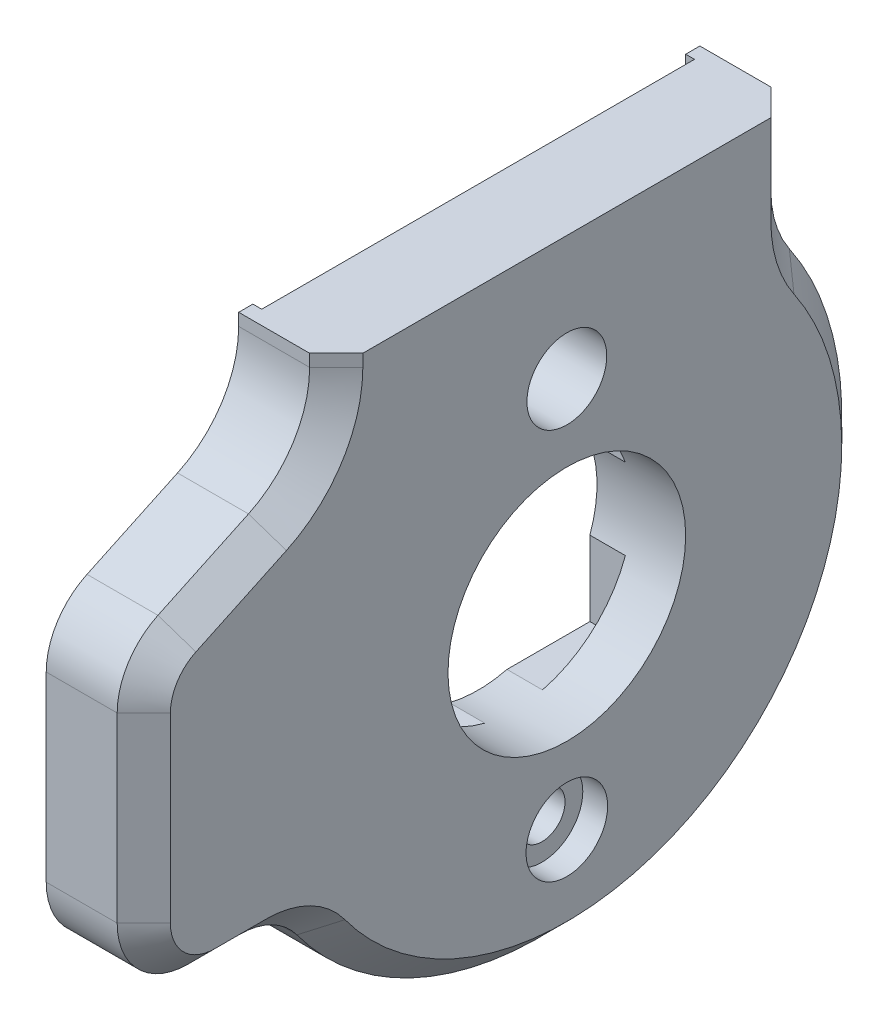
SolidWorks part; units mm, degrees
ref_plane "Front Plane" through (0, 0, 0) normal (0, 0, 1) x (1, 0, 0)
ref_plane "Top Plane" through (0, 0, 0) normal (0, 1, 0) x (1, 0, 0)
ref_plane "Right Plane" through (0, 0, 0) normal (1, 0, 0) x (0, 0, -1)
sketch "Sketch1" plane through (0, 0, 0) normal (1, 0, 0) x (0, 0, -1)
  line L0 (-53, 3.3371) -> (-53, -7.0385)
  line L1 (-82.9482, -28.4) -> (-85.85, -28.4)
  line L2 (-89.85, -24.4) -> (-89.85, -14.1397)
  line L3 (-87.5516, -10.5196) -> (-82.4476, -8.1205)
  line L4 (-79, -2.6905) -> (-79, 3.3371)
  arc A0 (-80.25, 7.0028) -> (-51.75, 7.0028) centre (-66, 18) cw
  arc A1 (-51.75, 7.0028) -> (-53, 3.3371) centre (-47, 3.3371) ccw
  arc A2 (-53, -7.0385) -> (-51.9565, -10.4198) centre (-47, -7.0385) ccw
  arc A3 (-51.9565, -10.4198) -> (-79.7199, -30.0381) centre (-66, -20) cw
  arc A4 (-79.7199, -30.0381) -> (-82.9482, -28.4) centre (-82.9482, -32.4) ccw
  arc A5 (-85.85, -28.4) -> (-89.85, -24.4) centre (-85.85, -24.4) cw
  arc A6 (-89.85, -14.1397) -> (-87.5516, -10.5196) centre (-85.85, -14.1397) cw
  arc A7 (-82.4476, -8.1205) -> (-79, -2.6905) centre (-85, -2.6905) ccw
  arc A8 (-79, 3.3371) -> (-80.25, 7.0028) centre (-85, 3.3371) ccw
extrude "Boss-Extrude1" add sketch "Sketch1" along normal blind 5.5 from offset 55.1
sketch "Sketch2" plane through (0, 0, 0) normal (1, 0, 0) x (0, 0, -1)
  line L0 (-53.8, 3.3371) -> (-53.8, -7.0385)
  line L1 (-82.9482, -27.6) -> (-85.85, -27.6)
  line L2 (-89.05, -24.4) -> (-89.05, -14.1397)
  line L3 (-87.2113, -11.2436) -> (-82.1073, -8.8446)
  line L4 (-78.2, -2.6905) -> (-78.2, 3.3371)
  arc A0 (-79.6167, 7.4916) -> (-52.3833, 7.4916) centre (-66, 18) cw
  arc A1 (-52.3833, 7.4916) -> (-53.8, 3.3371) centre (-47, 3.3371) ccw
  arc A2 (-53.8, -7.0385) -> (-52.6174, -10.8706) centre (-47, -7.0385) ccw
  arc A3 (-52.6174, -10.8706) -> (-79.0743, -29.5657) centre (-66, -20) cw
  arc A4 (-79.0743, -29.5657) -> (-82.9482, -27.6) centre (-82.9482, -32.4) ccw
  arc A5 (-85.85, -27.6) -> (-89.05, -24.4) centre (-85.85, -24.4) cw
  arc A6 (-89.05, -14.1397) -> (-87.2113, -11.2436) centre (-85.85, -14.1397) cw
  arc A7 (-82.1073, -8.8446) -> (-78.2, -2.6905) centre (-85, -2.6905) ccw
  arc A8 (-78.2, 3.3371) -> (-79.6167, 7.4916) centre (-85, 3.3371) ccw
extrude "Boss-Extrude2" add sketch "Sketch2" along normal blind 0.6 from offset 55 separate body
combine bodies "Combine1" operation type subtract main body 101 bodies to subtract 102
chamfer "Chamfer1" distance 1.5 angle 45 14 edges at (60.6, -5.9065, 79.9347) (60.6, -9.3201, 84.9996) (60.6, 0.3233, 79) (60.6, -11.9956, 89.2269) (60.6, 5.2736, 79.3211) (60.6, -19.2698, 89.85) (60.6, 36, 66) (60.6, -27.2284, 88.6784) (60.6, 5.2736, 52.6789) (60.6, -28.4, 84.3991) (60.6, -1.8507, 53) (60.6, -28.833, 81.1381) (60.6, -8.8078, 52.7332) (60.6, -33.8836, 56.1895)
sketch "Sketch3" plane through (0, 0, 0) normal (0, 0, 1) x (1, 0, 0)
  line L1 (55.5, -21) -> (59.6, -21)
  line L2 (55.5, -21) -> (55.5, -19)
  line L3 (55.5, -19) -> (59.6, -19)
  line L4 (59.6, -21) -> (59.6, -19)
extrude "Boss-Extrude3" add sketch "Sketch3" along normal blind 2.9 from offset 55.875 separate body
combine bodies "Combine2" operation type subtract main body 103 bodies to subtract 104
sketch "Sketch4" plane through (0, 0, 0) normal (0, 0, 1) x (1, 0, 0)
  line L1 (55.5, -21) -> (59.6, -21)
  line L2 (55.5, -21) -> (55.5, -19)
  line L3 (55.5, -19) -> (59.6, -19)
  line L4 (59.6, -21) -> (59.6, -19)
extrude "Boss-Extrude4" add sketch "Sketch4" along normal blind 2.9 from offset 84.025 separate body
combine bodies "Combine3" operation type subtract main body 105 bodies to subtract 106
sketch "Sketch5" plane through (0, 0, 0) normal (0, 0, 1) x (1, 0, 0)
  line L1 (55.5, -26.5) -> (57.6, -26.5)
  line L2 (55.5, -26.5) -> (55.5, -13.5)
  line L3 (55.5, -13.5) -> (57.6, -13.5)
  line L4 (57.6, -26.5) -> (57.6, -13.5)
extrude "Boss-Extrude5" add sketch "Sketch5" along normal blind 23.4 from offset 59.7 separate body
combine bodies "Combine4" operation type subtract main body 107 bodies to subtract 108
sketch "Sketch6" plane through (0, 0, 0) normal (1, 0, 0) x (0, 0, -1)
  circle A0 centre (-66, -20) radius 6.7
extrude "Boss-Extrude6" add sketch "Sketch6" along normal blind 5.6 from offset 55.5 separate body
combine bodies "Combine5" operation type subtract main body 109 bodies to subtract 110
sketch "Sketch7" plane through (0, 0, 0) normal (1, 0, 0) x (0, 0, -1)
  circle A0 centre (-66, -9) radius 2.25
extrude "Boss-Extrude7" add sketch "Sketch7" along normal blind 5.6 from offset 55.5 separate body
combine bodies "Combine6" operation type subtract main body 111 bodies to subtract 112
sketch "Sketch8" plane through (0, 0, 0) normal (1, 0, 0) x (0, 0, -1)
  circle A0 centre (-66, -31) radius 2.3
extrude "Boss-Extrude8" add sketch "Sketch8" along normal blind 1.9 from offset 59.2 separate body
combine bodies "Combine7" operation type subtract main body 113 bodies to subtract 114
sketch "Sketch9" plane through (0, 0, 0) normal (1, 0, 0) x (0, 0, -1)
  circle A0 centre (-66, -31) radius 1.3
extrude "Boss-Extrude9" add sketch "Sketch9" along normal blind 3.75 from offset 55.5 separate body
combine bodies "Combine8" operation type subtract main body 115 bodies to subtract 116
sketch "Sketch10" plane through (0, 0, 0) normal (0, 0, 1) x (1, 0, 0)
  line L1 (40, -2) -> (70, -2)
  line L2 (40, -2) -> (40, 60)
  line L3 (40, 60) -> (70, 60)
  line L4 (70, -2) -> (70, 60)
extrude "Boss-Extrude10" add sketch "Sketch10" along normal blind 80 from offset 26 separate body
combine bodies "Combine9" operation type subtract main body 117 bodies to subtract 118
